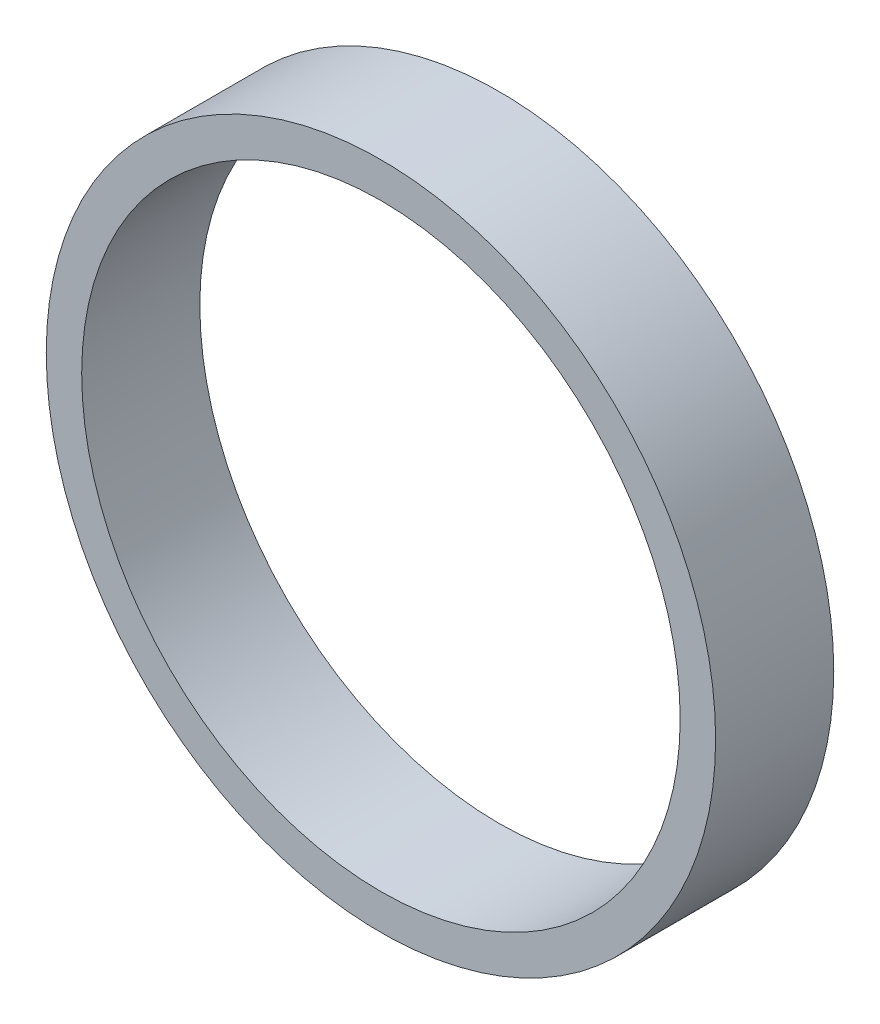
SolidWorks part; units mm, degrees
ref_plane "Front Plane" through (0, 0, 0) normal (0, 0, 1) x (1, 0, 0)
ref_plane "Top Plane" through (0, 0, 0) normal (0, 1, 0) x (1, 0, 0)
ref_plane "Right Plane" through (0, 0, 0) normal (1, 0, 0) x (0, 0, -1)
sketch "Sketch1" plane through (0, 0, 0) normal (0, 0, 1) x (1, 0, 0)
  circle A0 centre (0, 0) radius 53.975
  dimension "D1" = 107.95
extrude "Boss-Extrude1" add sketch "Sketch1" along normal blind 19.05
sketch "Sketch2" plane through (0, 0, 19.05) normal (0, 0, 1) x (1, 0, 0)
  circle A0 centre (0, 0) radius 48.26
  dimension "D1" = 96.52
extrude "Cut-Extrude1" cut sketch "Sketch2" against normal through all
